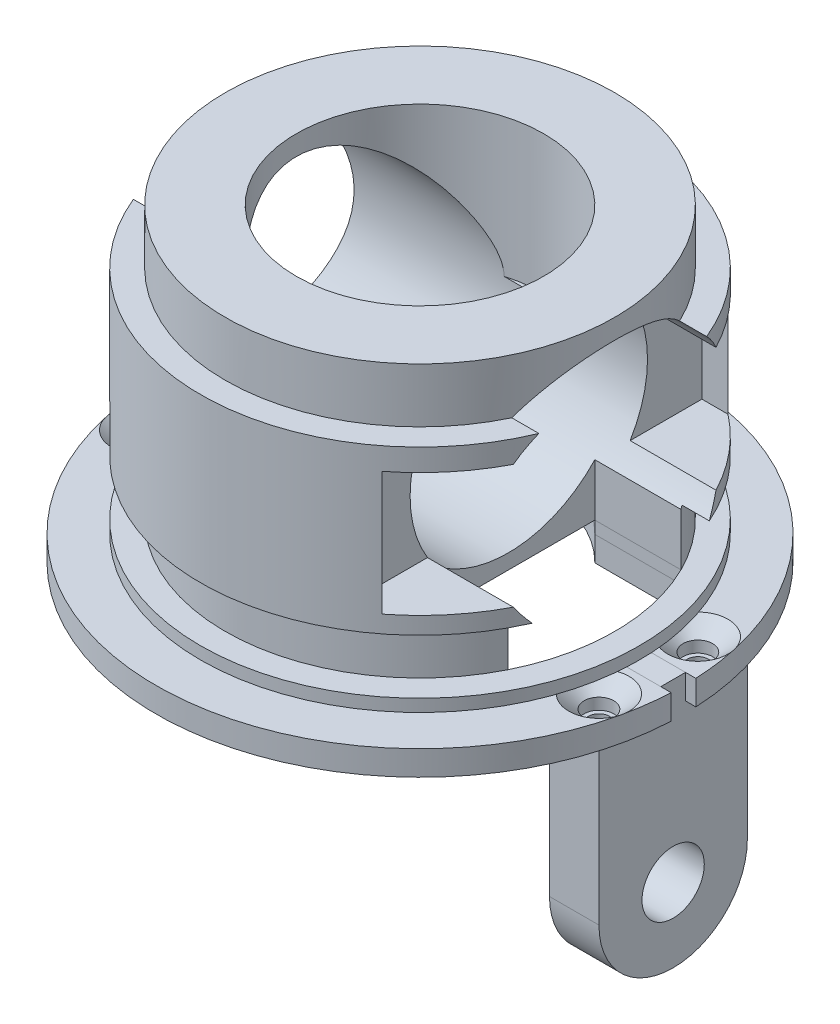
SolidWorks part; units mm, degrees
material "Alum Plate"
ref_plane "Front Plane" through (0, 0, 0) normal (0, 0, 1) x (1, 0, 0)
ref_plane "Top Plane" through (0, 0, 0) normal (0, 1, 0) x (1, 0, 0)
ref_plane "Right Plane" through (0, 0, 0) normal (1, 0, 0) x (0, 0, -1)
other "Bounding Box"
ref_plane "Default Plane" through (-8.9266, -12.7485, 0) normal (-0.1736, 0.9848, 0) x (0.9848, 0.1736, 0)
sketch "Sketch2" plane through (0, 0, 0) normal (1, 0, 0) x (0, 0, -1)
  line L0 (-25, 31.13) -> (25, 31.13) construction
  line L1 (-32.5, 31.13) -> (-25, 31.13)
  line L2 (-32.5, 31.13) -> (-32.5, 24.13)
  line L3 (-32.5, 24.13) -> (-25, 24.13)
  line L4 (-25, 31.13) -> (-25, 24.13)
  line L5 (-32.5, 31.13) -> (-25, 24.13) construction
  line L6 (-32.5, 24.13) -> (-25, 31.13) construction
  line L7 (25, 31.13) -> (32.5, 31.13)
  line L8 (25, 31.13) -> (25, 24.13)
  line L9 (25, 24.13) -> (32.5, 24.13)
  line L10 (32.5, 31.13) -> (32.5, 24.13)
  line L11 (25, 31.13) -> (32.5, 24.13) construction
  line L12 (25, 24.13) -> (32.5, 31.13) construction
  line L13 (-25, 24.13) -> (25, 24.13) construction
  line L14 (0, 0) -> (0, 24.13) construction
  line L15 (-25, 52.055) -> (25, 52.055) construction
  line L16 (25, 59.055) -> (-25, 59.055) construction
  line L17 (0, 31.13) -> (0, 52.055) construction
  line L18 (-32.5, 59.055) -> (-25, 59.055)
  line L19 (-32.5, 59.055) -> (-32.5, 52.055)
  line L20 (-32.5, 52.055) -> (-25, 52.055)
  line L21 (-25, 59.055) -> (-25, 52.055)
  line L22 (-32.5, 59.055) -> (-25, 52.055) construction
  line L23 (-32.5, 52.055) -> (-25, 59.055) construction
  line L24 (32.5, 59.055) -> (25, 59.055)
  line L25 (32.5, 59.055) -> (32.5, 52.055)
  line L26 (32.5, 52.055) -> (25, 52.055)
  line L27 (25, 59.055) -> (25, 52.055)
  line L28 (32.5, 59.055) -> (25, 52.055) construction
  line L29 (32.5, 52.055) -> (25, 59.055) construction
  line L30 (-9.525, 0) -> (-9.525, 24.13)
  line L31 (9.525, 0) -> (9.525, 24.13)
  line L34 (-77.1082, -22.225) -> (-30.51, -22.225) construction
  line L35 (-32.5, 31.13) -> (32.5, 31.13)
  line L36 (-32.5, 31.13) -> (-32.5, 37.48)
  line L37 (-32.5, 37.48) -> (32.5, 37.48)
  line L38 (32.5, 31.13) -> (32.5, 37.48)
  line L40 (-97.0753, 79.375) -> (-40, 79.375) construction
  circle A0 centre (0, 0) radius 22.225
  circle A1 centre (0, 0) radius 18
  circle A2 centre (0, 41.275) radius 14
  arc A3 (-9.525, 0) -> (9.525, 0) centre (0, 0) ccw
  circle A4 centre (0, 0) radius 4
  point P3 (-28.75, 27.63)
  point P8 (28.75, 27.63)
  point P16 (-28.75, 55.555)
  point P22 (28.75, 55.555)
  point P35 (0, -9.525)
  point P36 (-14, 41.275)
  point P37 (-18, 0)
  point P39 (-22.225, 0)
  dimension "D1" = 44.45
  dimension "D5" = 36
  dimension "D6" = 28
  dimension "D7" = 81.28
  dimension "D8" = 34.925
  dimension "D12" = 8
  dimension "D2" = 65
  dimension "D3" = 50
  dimension "D4" = 7
  dimension "D9" = 6.35
  dimension "D10" = 41.275
  dimension "D11" = 19.05
  dimension "D14" = 101.6
sketch "Sketch3" plane through (0, 0, 0) normal (0, 1, 0) x (1, 0, 0)
  line L0 (-16.03, 0) -> (13.97, 0) construction
  line L6 (-9.525, 22.225) -> (9.525, 22.225)
  line L7 (-16.03, 14) -> (13.97, 14)
  line L8 (-16.03, 14) -> (-16.03, -14)
  line L9 (-16.03, -14) -> (13.97, -14)
  line L10 (13.97, 14) -> (13.97, -14)
  line L11 (-16.03, 14) -> (13.97, -14) construction
  line L12 (-16.03, -14) -> (13.97, 14) construction
  line L13 (-9.525, 22.225) -> (-9.525, -22.225)
  line L14 (-9.525, -22.225) -> (9.525, -22.225)
  line L20 (9.525, 22.225) -> (9.525, -22.225)
  line L21 (-9.525, 22.225) -> (9.525, -22.225) construction
  line L22 (15.97, 9.017) -> (22.97, 9.017)
  line L23 (15.97, 9.017) -> (15.97, -9.017)
  line L24 (15.97, -9.017) -> (22.97, -9.017)
  line L25 (22.97, 9.017) -> (22.97, -9.017)
  line L26 (15.97, 9.017) -> (22.97, -9.017) construction
  line L27 (15.97, -9.017) -> (22.97, 9.017) construction
  line L32 (-9.525, -22.225) -> (9.525, 22.225) construction
  line L33 (-23.03, 18) -> (13.97, 18)
  line L34 (-23.03, 18) -> (-23.03, -18)
  line L39 (-23.03, -18) -> (13.97, -18)
  line L40 (13.97, 18) -> (13.97, -18)
  line L45 (-23.03, 18) -> (13.97, -18) construction
  line L46 (-23.03, -18) -> (13.97, 18) construction
  line L47 (22.97, -9.017) -> (33.5214, -9.017)
  line L48 (22.97, -9.017) -> (22.97, 9.017)
  line L49 (22.97, 9.017) -> (33.5214, 9.017)
  line L50 (33.5214, -9.017) -> (33.5214, 9.017)
  line L51 (22.97, -9.017) -> (33.5214, 9.017) construction
  line L52 (22.97, 9.017) -> (33.5214, -9.017) construction
  circle A0 centre (0, 0) radius 25
  circle A1 centre (0, 0) radius 32.5
  point P3 (0, 0)
  point P5 (-1.03, 0)
  point P8 (-4.53, 0)
  point P29 (19.47, 0)
  point P50 (28.2457, 0)
  dimension "D6" = 17.5514
  dimension "D1" = 30
  dimension "D2" = 18.034
  dimension "D3" = 19.05
  dimension "D4" = 37
  dimension "D5" = 7
  dimension "D7" = 2
  dimension "D8" = 13.97
ref_plane "Plane1" through (0, 24.13, 0) normal (0, 1, 0) x (1, 0, 0)
sketch "Sketch4" plane through (0, 24.13, 0) normal (0, 1, 0) x (1, 0, 0)
  line L0 (22.3945, 11.1125) -> (11.337, 11.1125)
  line L1 (22.3945, -11.1125) -> (11.337, -11.1125)
  line L2 (15.875, 0) -> (25, 0) construction
  line L3 (16.8657, -11.1125) -> (16.8657, 0) construction
  line L4 (16.8657, 0) -> (16.8657, 11.1125) construction
  circle A0 centre (0, 0) radius 32.5
  circle A1 centre (0, 0) radius 32.5 construction
  arc A2 (11.337, 11.1125) -> (11.337, -11.1125) centre (0, 0) ccw
  arc A3 (22.3945, -11.1125) -> (22.3945, 11.1125) centre (0, 0) ccw
  circle A4 centre (0, 0) radius 25 construction
  arc A5 (11.337, -11.1125) -> (15.875, 0) centre (0, 0) ccw construction
  arc A6 (15.875, 0) -> (11.337, 11.1125) centre (0, 0) ccw construction
  dimension "D1" = 31.75
  dimension "D2" = 22.225
extrude "Boss-Extrude1" add sketch "Sketch4" against normal blind 3.175 from offset 1.5875 offset against normal yes
sketch "Sketch5" plane through (0, 19.3675, 0) normal (0, -1, 0) x (1, 0, 0)
  line L0 (-32.5, 0) -> (32.5, 0) construction
  line L1 (-32.5, -9.525) -> (-26.15, -9.525)
  line L2 (-32.5, -9.525) -> (-32.5, 9.525)
  line L3 (-32.5, 9.525) -> (-26.15, 9.525)
  line L4 (-26.15, -9.525) -> (-26.15, 9.525)
  line L5 (-32.5, -9.525) -> (-26.15, 9.525) construction
  line L6 (-32.5, 9.525) -> (-26.15, -9.525) construction
  line L7 (32.5, -9.525) -> (26.15, -9.525)
  line L8 (32.5, -9.525) -> (32.5, 9.525)
  line L9 (32.5, 9.525) -> (26.15, 9.525)
  line L10 (26.15, -9.525) -> (26.15, 9.525)
  line L11 (32.5, -9.525) -> (26.15, 9.525) construction
  line L12 (32.5, 9.525) -> (26.15, -9.525) construction
  circle A0 centre (0, 0) radius 32.5 construction
  point P0 (-29.325, 0)
  point P5 (29.325, 0)
  point P10 (28.7975, 0)
  point P16 (-28.3234, 0)
  point P17 (-25.7634, 10.2145)
  point P18 (-26.15, -10.5633)
  dimension "D1" = 6.35
  dimension "D2" = 6.35
extrude "Boss-Extrude2" add sketch "Sketch5" along normal up to vertex (28.8925 mm away) separate body up to point (0, -9.525, 0)
sketch "Sketch6" plane through (32.5, 0, 0) normal (1, 0, 0) x (0, 0, -1)
  line L0 (-9.525, 0) -> (-9.525, -9.525)
  line L2 (9.525, -9.525) -> (9.525, 0)
  line L3 (9.525, -9.525) -> (-9.525, -9.525) construction
  circle A1 centre (0, 0) radius 4 construction
  arc A2 (-9.525, 0) -> (9.525, 0) centre (0, 0) ccw
  circle A3 centre (0, 0) radius 4
  arc A4 (9.525, -9.525) -> (-9.525, -9.525) centre (0, -9.525) cw
  point P11 (0, 0)
  point P14 (0, -9.525)
extrude "Cut-Extrude1" cut sketch "Sketch6" against normal through all
sketch "Sketch7" plane through (0, 22.5425, 0) normal (0, 1, 0) x (1, 0, 0)
  line L0 (-29.325, -9.525) -> (-29.325, -6.35) construction
  line L1 (-29.325, -6.35) -> (-29.325, 6.35) construction
  line L2 (-29.325, 6.35) -> (-29.325, 9.525) construction
  line L3 (29.325, -9.525) -> (29.325, -6.35) construction
  line L4 (-26.15, -9.525) -> (-26.15, 9.525)
  line L5 (-26.15, 9.525) -> (-32.5, 9.525)
  line L6 (-32.5, 9.525) -> (-32.5, -9.525)
  line L7 (-32.5, -9.525) -> (-26.15, -9.525)
  line L8 (-26.15, -9.525) -> (-26.15, 9.525) construction
  line L9 (-26.15, 9.525) -> (-32.5, 9.525) construction
  line L10 (-32.5, 9.525) -> (-32.5, -9.525) construction
  line L11 (-32.5, -9.525) -> (-26.15, -9.525) construction
  line L12 (26.15, 9.525) -> (26.15, -9.525)
  line L13 (26.15, -9.525) -> (32.5, -9.525)
  line L14 (32.5, -9.525) -> (32.5, 9.525)
  line L15 (32.5, 9.525) -> (26.15, 9.525)
  line L16 (26.15, 9.525) -> (26.15, -9.525) construction
  line L17 (26.15, -9.525) -> (32.5, -9.525) construction
  line L18 (32.5, -9.525) -> (32.5, 9.525) construction
  line L19 (32.5, 9.525) -> (26.15, 9.525) construction
  line L20 (29.325, -6.35) -> (29.325, 6.35) construction
  line L21 (29.325, 6.35) -> (29.325, 9.525) construction
  line L22 (-29.325, 6.35) -> (-32.5, 6.35) construction
  circle A0 centre (-29.325, -6.35) radius 1.8986
  circle A1 centre (-29.325, 6.35) radius 1.8986
  circle A2 centre (29.325, -6.35) radius 1.8986
  circle A3 centre (29.325, 6.35) radius 1.8986
  circle A4 centre (-29.325, 0) radius 1.8986 construction
  circle A5 centre (29.325, 0) radius 1.8986 construction
  dimension "D3" = 3.7973
  dimension "D1" = 0
  dimension "D2" = 0
extrude "Cut-Extrude2" cut sketch "Sketch7" against normal through all
sketch "Sketch8" plane through (0, 22.5425, 0) normal (0, 1, 0) x (1, 0, 0)
  circle A0 centre (0, 0) radius 32.5 construction
  circle A1 centre (0, 0) radius 32.5
  circle A2 centre (0, 0) radius 33.867
extrude "Boss-Extrude3" add sketch "Sketch8" against normal up to surface (3.175 mm away) up to face at (-29.325, 19.3675, -4.4514)
sketch "Sketch9" plane through (0, 22.5425, 0) normal (0, 1, 0) x (1, 0, 0)
  circle A0 centre (-29.325, 6.35) radius 1.3526
  circle A2 centre (-29.325, -6.35) radius 1.3526
  circle A3 centre (29.325, 6.35) radius 1.3526
  circle A5 centre (29.325, -6.35) radius 1.3526
  dimension "D1" = 2.7051
extrude "Cut-Extrude3" cut sketch "Sketch9" against normal blind 12.7
chamfer "Chamfer1" distance 1.9748 angle 41 4 edges at (29.325, 22.5425, 8.2486) (29.325, 22.5425, -4.4514) (-29.325, 22.5425, 8.2486) (-29.325, 22.5425, -4.4514) first distance on face at (-29.325, 22.5425, -4.4514)
sketch "Sketch10" plane through (0, 22.5425, 0) normal (0, 1, 0) x (1, 0, 0)
  line L0 (-26.15, -4) -> (-26.15, 4) construction
  line L1 (-33.8298, -1.5875) -> (-26.15, -1.5875)
  line L2 (-33.8298, -1.5875) -> (-33.8298, 1.5875) construction
  line L3 (-33.8298, 1.5875) -> (-26.15, 1.5875)
  line L4 (-26.15, -1.5875) -> (-26.15, 1.5875)
  line L5 (-33.8298, -1.5875) -> (-26.15, 1.5875) construction
  line L6 (-33.8298, 1.5875) -> (-26.15, -1.5875) construction
  line L12 (0, -25) -> (0, 25) construction
  line L14 (0, -33.867) -> (0, 33.867) construction
  line L15 (0, -32.5) -> (0, -25) construction
  line L16 (33.8298, -1.5875) -> (26.15, -1.5875)
  line L17 (26.15, -1.5875) -> (26.15, 1.5875)
  line L18 (33.8298, 1.5875) -> (26.15, 1.5875)
  arc A0 (-33.1644, 6.8628) -> (-33.1644, -6.8628) centre (0, 0) ccw construction
  arc A2 (-33.8298, -1.5875) -> (-33.8298, 1.5875) centre (0, 0) cw
  arc A3 (33.0326, 7.4715) -> (-33.0326, 7.4715) centre (0, 0) ccw construction
  arc A4 (-33.0326, -7.4715) -> (33.0326, -7.4715) centre (0, 0) ccw construction
  arc A5 (33.8298, -1.5875) -> (33.8298, 1.5875) centre (0, 0) ccw
  point P4 (-29.9899, 0)
  point P9 (0, -33.867)
  dimension "D1" = 3.175
extrude "Cut-Extrude4" cut sketch "Sketch10" against normal through all
sketch "Sketch11" plane through (-32.5, 0, 0) normal (-1, 0, 0) x (0, 0, 1)
  line L4 (1.5875, 19.3675) -> (1.5875, 22.5425)
  line L5 (1.5875, 22.5425) -> (-1.5875, 22.5425)
  line L6 (-1.5875, 22.5425) -> (-1.5875, 19.3675)
  line L7 (-1.5875, 19.3675) -> (1.5875, 19.3675)
  line L8 (1.5875, 19.3675) -> (1.5875, 22.5425)
  line L9 (1.5875, 22.5425) -> (-1.5875, 22.5425)
  line L10 (-1.5875, 22.5425) -> (-1.5875, 19.3675)
  line L11 (-1.5875, 19.3675) -> (1.5875, 19.3675)
  dimension "D1" = 0
extrude "Boss-Extrude4" add sketch "Sketch11" against normal up to surface (6.35 mm away) up to face at (-26.15, 0, 4)
sketch "Sketch12" plane through (32.5, 0, 0) normal (1, 0, 0) x (0, 0, -1)
  line L4 (1.5875, 19.3675) -> (1.5875, 22.5425)
  line L5 (1.5875, 22.5425) -> (-1.5875, 22.5425)
  line L6 (-1.5875, 22.5425) -> (-1.5875, 19.3675)
  line L7 (-1.5875, 19.3675) -> (1.5875, 19.3675)
  line L8 (1.5875, 19.3675) -> (1.5875, 22.5425)
  line L9 (1.5875, 22.5425) -> (-1.5875, 22.5425)
  line L10 (-1.5875, 22.5425) -> (-1.5875, 19.3675)
  line L11 (-1.5875, 19.3675) -> (1.5875, 19.3675)
  dimension "D1" = 0
extrude "Boss-Extrude5" add sketch "Sketch12" against normal up to surface (6.35 mm away) up to face at (26.15, 0, -4)
sketch "Sketch13" plane through (0, 22.5425, 0) normal (0, 1, 0) x (1, 0, 0)
  line L2 (11.337, -11.1125) -> (22.3945, -11.1125)
  line L3 (22.3945, 11.1125) -> (11.337, 11.1125)
  line L4 (11.337, -11.1125) -> (22.3945, -11.1125)
  line L5 (22.3945, 11.1125) -> (11.337, 11.1125)
  circle A0 centre (0, 0) radius 28.175
  circle A1 centre (0, 0) radius 25 construction
  arc A2 (22.3945, -11.1125) -> (22.3945, 11.1125) centre (0, 0) ccw
  arc A3 (11.337, 11.1125) -> (11.337, -11.1125) centre (0, 0) ccw
  arc A4 (22.3945, -11.1125) -> (22.3945, 11.1125) centre (0, 0) ccw
  arc A5 (11.337, 11.1125) -> (11.337, -11.1125) centre (0, 0) ccw
  dimension "D2" = 3.175
  dimension "D1" = 0
extrude "Boss-Extrude6" add sketch "Sketch13" along normal up to surface (1.5875 mm away) separate body up to plane "Plane1"
sketch "Sketch14" plane through (0, 0, 0) normal (1, 0, 0) x (0, 0, -1)
  line L0 (0, 24.13) -> (25, 24.13)
  line L1 (25, 24.13) -> (25, 31.13)
  line L2 (25, 31.13) -> (28.175, 31.13)
  line L3 (25, 31.13) -> (32.5, 31.13) construction
  line L4 (28.175, 31.13) -> (28.175, 52.055)
  line L5 (32.5, 52.055) -> (25, 52.055) construction
  line L6 (28.175, 52.055) -> (25, 52.055)
  line L7 (25, 52.055) -> (25, 59.055)
  line L8 (0, 24.13) -> (0, 59.055)
  line L9 (25, 59.055) -> (-25, 59.055) construction
  line L10 (0, 59.055) -> (25, 59.055)
  dimension "D1" = 3.175
revolve "Revolve1" add sketch "Sketch14" angle 360 about L8
sketch "Sketch15" plane through (0, 0, 0) normal (1, 0, 0) x (0, 0, -1)
  circle A0 centre (0, 41.275) radius 15.24
  dimension "D1" = 30.48
extrude "Cut-Extrude5" cut sketch "Sketch15" against normal through all both and the other way through all
sketch "Sketch17" plane through (0, 24.13, 0) normal (0, -1, 0) x (1, 0, 0)
  line L0 (11.337, -11.1125) -> (11.337, 11.1125)
  line L2 (22.3945, 11.1125) -> (11.337, 11.1125)
  line L3 (11.337, -11.1125) -> (22.3945, -11.1125)
  line L4 (22.3945, 11.1125) -> (11.337, 11.1125)
  line L5 (11.337, -11.1125) -> (22.3945, -11.1125)
  arc A2 (22.3945, -11.1125) -> (22.3945, 11.1125) centre (0, 0) ccw
  arc A3 (11.337, 11.1125) -> (11.337, -11.1125) centre (0, 0) ccw
  arc A4 (22.3945, -11.1125) -> (22.3945, 11.1125) centre (0, 0) ccw
  dimension "D1" = 0
extrude "Cut-Extrude8" cut sketch "Sketch17" against normal up to vertex (17.145 mm away) up to point (0, 41.275, 0)
sketch "Sketch18" plane through (0, 59.055, 0) normal (0, 1, 0) x (1, 0, 0)
  circle A0 centre (0, 0) radius 15.875
  arc A1 (11.337, 11.1125) -> (11.337, -11.1125) centre (0, 0) ccw construction
extrude "Cut-Extrude9" cut sketch "Sketch18" against normal up to vertex (17.78 mm away) up to point (0, 41.275, 0)
ref_plane "Plane2" through (13.97, 0, 0) normal (1, 0, 0) x (0, 0, -1)
sketch "Sketch19" plane through (13.97, 0, 0) normal (1, 0, 0) x (0, 0, -1)
  line L1 (-22.225, 49.2125) -> (22.225, 49.2125)
  line L2 (-22.225, 49.2125) -> (-22.225, 33.3375)
  line L3 (-22.225, 33.3375) -> (22.225, 33.3375)
  line L4 (22.225, 49.2125) -> (22.225, 33.3375)
  line L5 (-22.225, 49.2125) -> (22.225, 33.3375) construction
  line L6 (-22.225, 33.3375) -> (22.225, 49.2125) construction
  point P0 (0, 41.275)
  dimension "D1" = 15.875
  dimension "D2" = 44.45
extrude "Cut-Extrude10" cut sketch "Sketch19" along normal through all
